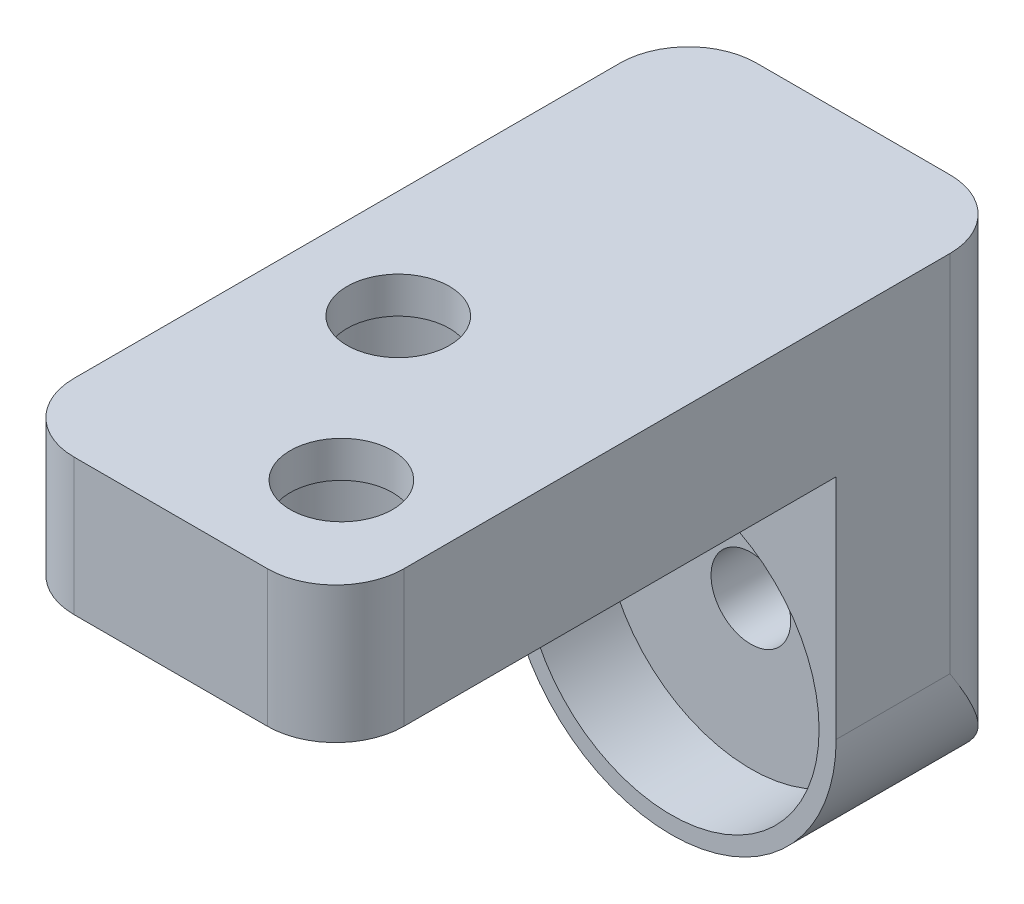
SolidWorks part; units mm, degrees
ref_plane "Ebene vorne" through (0, 0, 0) normal (0, 0, 1) x (1, 0, 0)
ref_plane "Ebene oben" through (0, 0, 0) normal (0, 1, 0) x (1, 0, 0)
ref_plane "Ebene rechts" through (0, 0, 0) normal (1, 0, 0) x (0, 0, -1)
sketch "Skizze1" plane through (0, 0, 0) normal (0, 0, 1) x (1, 0, 0)
  line L1 (0, 0) -> (14.5, 0)
  line L2 (0, 0) -> (0, 23.25)
  line L3 (0, 23.25) -> (14.5, 23.25)
  line L4 (14.5, 0) -> (14.5, 23.25)
  dimension "D1" = 23.25
  dimension "D2" = 14.5
extrude "Aufsatz-Linear austragen1" add sketch "Skizze1" along normal blind 30
sketch "Skizze5" plane through (14.5, 0, 0) normal (1, 0, 0) x (0, 0, -1)
  line L1 (-30, 0) -> (-8, 0)
  line L2 (-30, 0) -> (-30, 17.25)
  line L3 (-30, 17.25) -> (-8, 17.25)
  line L4 (-8, 0) -> (-8, 17.25)
  dimension "D1" = 22
  dimension "D2" = 17.25
extrude "Schnitt-Linear austragen3" cut sketch "Skizze5" against normal through all
fillet "Verrundung1" radius 7.25 2 edges at (14.5, 0, 4) (0, 0, 4)
hole_wizard "Stirnsenkung für M4 Zylinderschraube mit Innensechskant1" positions "Skizze8" profile "Skizze7" counterbore size "M4" standard "DIN" end condition through all
sketch "Skizze8" plane through (0, 17.25, 0) normal (0, -1, 0) x (-1, 0, 0)
  line L0 (0, -8) -> (0, -30) construction
  line L1 (0, -30) -> (-14.5, -30) construction
  point P0 (-4.75, -17.5)
  point P2 (-9.75, -25)
  dimension "D1" = 4.75
  dimension "D2" = 5
  dimension "D3" = 5
  dimension "D4" = 7.5
sketch "Skizze7" plane through (4.75, 17.25, 17.5) normal (1, 0, 0) x (0, 0, -1)
  line L0 (0, 0) -> (0, 6)
  line L1 (0, 6) -> (2.25, 6)
  line L3 (2.25, 6) -> (2.25, 4.4)
  line L4 (2.25, 4.4) -> (4, 4.4)
  line L5 (4, 4.4) -> (4, 0)
  line L7 (4, 0) -> (0, 0)
  line L11 (0, -6.35) -> (0, 107.95) construction
  dimension "Bohrerdurchmesser" = 4.5
  dimension "Bohrungstiefe" = 6
  dimension "Senkdurchmesser2" = 8
  dimension "Senktiefe2" = 4.4
sketch "Skizze9" plane through (0, 0, 8) normal (0, 0, 1) x (1, 0, 0)
  circle A0 centre (7.25, 7.25) radius 6.5
  dimension "D1" = 13
extrude "Schnitt-Linear austragen4" cut sketch "Skizze9" against normal blind 3.5
sketch "Skizze10" plane through (0, 0, 4.5) normal (0, 0, 1) x (1, 0, 0)
  circle A0 centre (7.25, 7.25) radius 1.75
  dimension "D1" = 3.5
extrude "Schnitt-Linear austragen5" cut sketch "Skizze10" against normal blind 5.5
sketch "Skizze11" plane through (0, 23.25, 0) normal (0, 1, 0) x (1, 0, 0)
  line L0 (14.5, -30) -> (0, -30) construction
  line L1 (3, 0) -> (11.5, 0)
  line L2 (0, -3) -> (0, -27)
  line L3 (3, -30) -> (11.5, -30)
  line L4 (14.5, -3) -> (14.5, -27)
  arc A0 (0, -27) -> (3, -30) centre (3, -27) ccw
  arc A1 (11.5, -30) -> (14.5, -27) centre (11.5, -27) ccw
  arc A2 (11.5, 0) -> (14.5, -3) centre (11.5, -3) cw
  arc A3 (3, 0) -> (0, -3) centre (3, -3) ccw
  point P11 (14.5, -30)
  point P16 (0, 0)
  dimension "D1" = 3
extrude "Schnitt-Linear austragen6" cut sketch "Skizze11" against normal through all flip side to cut
